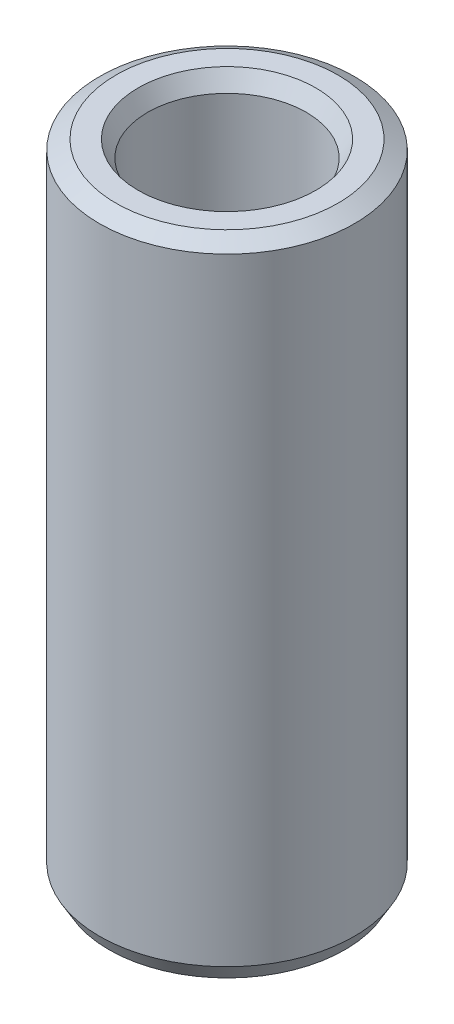
SolidWorks part; units mm, degrees
ref_plane "Front Plane" through (0, 0, 0) normal (0, 0, 1) x (1, 0, 0)
ref_plane "Top Plane" through (0, 0, 0) normal (0, 1, 0) x (1, 0, 0)
ref_plane "Right Plane" through (0, 0, 0) normal (1, 0, 0) x (0, 0, -1)
sketch "Sketch1" plane through (0, 0, 0) normal (0, 1, 0) x (1, 0, 0)
  circle A0 centre (0, 0) radius 50
  dimension "SLEEVE_OD" = 100
extrude "Boss-Extrude1" add sketch "Sketch1" along normal blind 252.1879
sketch "Sketch2" plane through (0, 0, 0) normal (0, 1, 0) x (1, 0, 0)
  circle A0 centre (0, 0) radius 31.1156
  dimension "BORE_D" = 62.2312
extrude "Cut-Extrude1" cut sketch "Sketch2" along normal through all
chamfer "Chamfer1" distance 3.722 angle 60 4 edges at (0, 252.1879, 31.1156) (0, 0, 31.1156) (0, 0, 50) (0, 252.1879, 50) first distance on face at (0, 252.1879, 31.1156) first distance on face at (0, 0, 31.1156) first distance on face at (0, 252.1879, 50)
